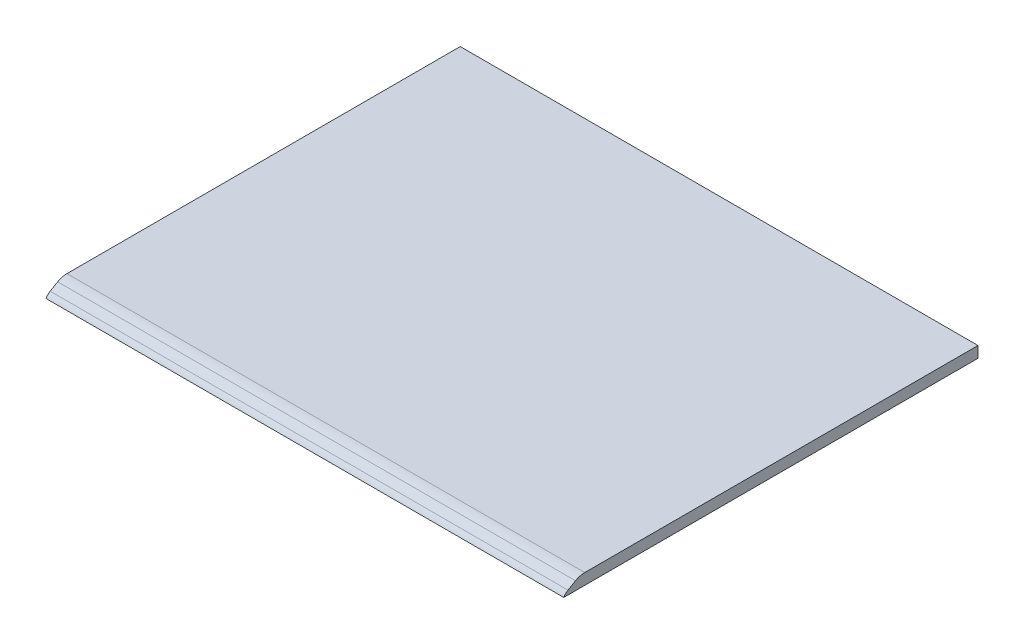
SolidWorks part; units mm, degrees
ref_plane "Спереди XY" through (0, 0, 0) normal (0, 0, 1) x (1, 0, 0)
ref_plane "Сверху XZ" through (0, 0, 0) normal (0, 1, 0) x (1, 0, 0)
ref_plane "Справа ZY" through (0, 0, 0) normal (1, 0, 0) x (0, 0, -1)
sketch "Эскиз1" plane through (0, 0, 0) normal (0, 1, 0) x (1, 0, 0)
  line L1 (-70, 56) -> (70, 56)
  line L2 (-70, 56) -> (-70, -56)
  line L3 (-70, -56) -> (70, -56)
  line L4 (70, 56) -> (70, -56)
  line L5 (-70, 56) -> (70, -56) construction
  line L6 (-70, -56) -> (70, 56) construction
  point P0 (0, 0)
  dimension "D1" = 140
  dimension "D2" = 112
extrude "Бобышка-Вытянуть1" add sketch "Эскиз1" along normal blind 3
chamfer "Фаска1" distance 2.5 angle 60 1 edges at (0, 3, 56) first distance on face at (0, 1.5, 56)
fillet "Скругление1" radius 5 1 edges at (0, 3, 51.6699)
fillet "Скругление2" radius 3 1 edges at (0, 0.5, 56)
